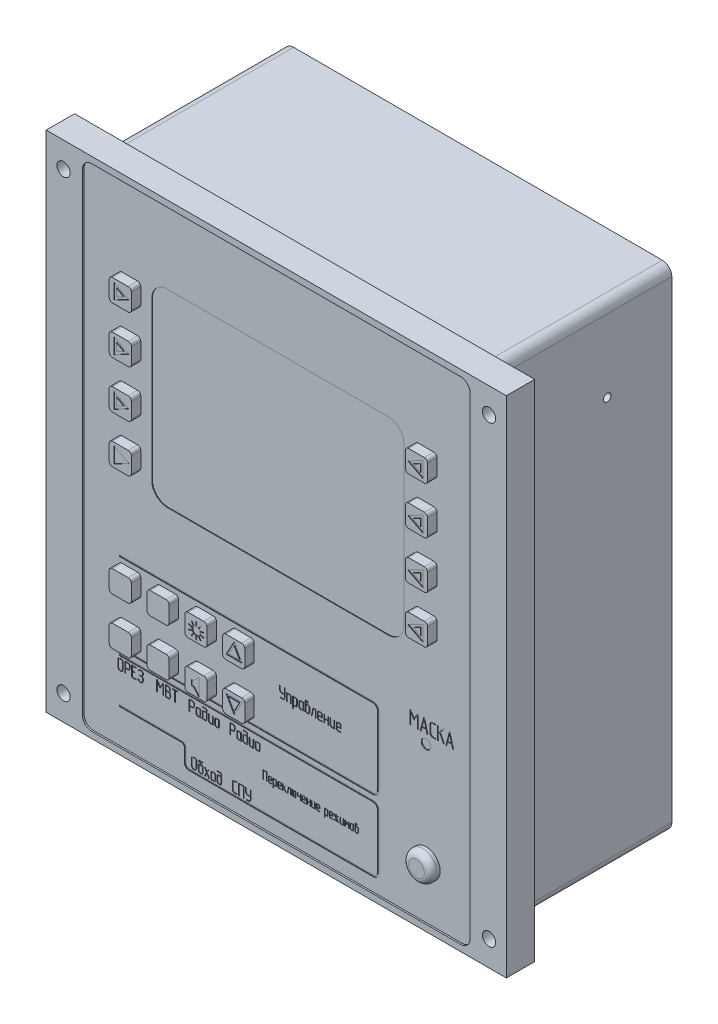
SolidWorks part; units mm, degrees
ref_plane "Спереди" through (0, 0, 0) normal (0, 0, 1) x (1, 0, 0)
ref_plane "Сверху" through (0, 0, 0) normal (0, 1, 0) x (1, 0, 0)
ref_plane "Справа" through (0, 0, 0) normal (1, 0, 0) x (0, 0, -1)
sketch "Эскиз1" plane through (0, 0, 0) normal (0, 0, 1) x (1, 0, 0)
  line L1 (-73, 80) -> (73, 80)
  line L2 (-73, 80) -> (-73, -80)
  line L3 (-73, -80) -> (73, -80)
  line L4 (73, 80) -> (73, -80)
  line L5 (0, -80) -> (0, 80) construction
  line L6 (-73, 0) -> (73, 0) construction
  point P0 (0, 0)
  dimension "D1" = 146
  dimension "D2" = 160
extrude "Бобышка-Вытянуть1" add sketch "Эскиз1" along normal mid plane 9
sketch "Эскиз3" plane through (0, 0, -4.5) normal (0, 0, -1) x (-1, 0, 0)
  line L1 (-61.5, 78) -> (61.5, 78)
  line L2 (-61.5, 78) -> (-61.5, -78)
  line L3 (-61.5, -78) -> (61.5, -78)
  line L4 (61.5, 78) -> (61.5, -78)
  line L5 (0, -78) -> (0, 78) construction
  line L6 (-61.5, 0) -> (61.5, 0) construction
  point P0 (0, 0)
  dimension "D1" = 123
  dimension "D2" = 156
extrude "Бобышка-Вытянуть2" add sketch "Эскиз3" along normal blind 55
fillet "Скругление1" radius 3 4 edges at (-61.5, -78, -32) (61.5, -78, -32) (61.5, 78, -32) (-61.5, 78, -32)
sketch "Эскиз4" plane through (0, 0, -59.5) normal (0, 0, -1) x (-1, 0, 0)
  line L0 (-73, -80) -> (-73, 80) construction
  line L1 (73, -80) -> (-73, -80) construction
  line L2 (-49, -51.3122) -> (-49, -72.7557) construction
  line L3 (-57.2172, -62) -> (-38.8096, -62) construction
  line L5 (-54.9, -56.1) -> (-43.1, -56.1) construction
  line L6 (-54.9, -56.1) -> (-54.9, -67.9) construction
  line L7 (-54.9, -67.9) -> (-43.1, -67.9) construction
  line L8 (-43.1, -56.1) -> (-43.1, -67.9) construction
  line L9 (-49, -67.9) -> (-49, -56.1) construction
  line L10 (-54.9, -62) -> (-43.1, -62) construction
  circle A0 centre (-49, -62) radius 5
  circle A1 centre (-54.9, -56.1) radius 1.1
  circle A2 centre (-43.1, -56.1) radius 1.1
  circle A3 centre (-43.1, -67.9) radius 1.1
  circle A4 centre (-54.9, -67.9) radius 1.1
  dimension "D1" = 24
  dimension "D2" = 18
  dimension "D3" = 10
  dimension "D5" = 2.2
  dimension "D6" = 11.8
  dimension "D4" = 11.8
extrude "Вырез-Вытянуть1" cut sketch "Эскиз4" against normal blind 20
sketch "Эскиз5" plane through (0, 0, -59.5) normal (0, 0, -1) x (-1, 0, 0)
  line L0 (-73, -80) -> (-73, 80) construction
  line L1 (73, -80) -> (-73, -80) construction
  line L3 (-53.75, 71.5) -> (-32.25, 71.5) construction
  line L4 (-53.75, 71.5) -> (-53.75, 50) construction
  line L5 (-53.75, 50) -> (-32.25, 50) construction
  line L6 (-32.25, 71.5) -> (-32.25, 50) construction
  line L7 (-43, 50) -> (-43, 71.5) construction
  line L8 (-53.75, 60.75) -> (-32.25, 60.75) construction
  circle A0 centre (-43, 60.75) radius 11
  circle A1 centre (-53.75, 71.5) radius 1.35
  circle A2 centre (-32.25, 71.5) radius 1.35
  circle A3 centre (-32.25, 50) radius 1.35
  circle A4 centre (-53.75, 50) radius 1.35
  dimension "D1" = 22
  dimension "D2" = 30
  dimension "D3" = 140.75
  dimension "D5" = 2.7
  dimension "D6" = 21.5
  dimension "D4" = 21.5
extrude "Вырез-Вытянуть2" cut sketch "Эскиз5" against normal blind 20
sketch "Эскиз6" plane through (0, 0, 4.5) normal (0, 0, 1) x (1, 0, 0)
  line L0 (67.5, 72) -> (67.5, -72) construction
  line L1 (-67.5, 72) -> (67.5, 72) construction
  line L3 (-67.5, -72) -> (67.5, -72) construction
  line L5 (0, -72) -> (0, 72) construction
  line L6 (-67.5, 0) -> (67.5, 0) construction
  line L7 (-67.5, 72) -> (-67.5, -72) construction
  circle A0 centre (-67.5, 72) radius 2.1
  circle A1 centre (67.5, 72) radius 2.1
  circle A2 centre (67.5, -72) radius 2.1
  circle A3 centre (-67.5, -72) radius 2.1
  point P1 (0, 0)
  dimension "D3" = 4.2
  dimension "D1" = 135
  dimension "D2" = 144
extrude "Вырез-Вытянуть3" cut sketch "Эскиз6" against normal blind 20
sketch "Эскиз7" plane through (61.5, 0, 0) normal (1, 0, 0) x (0, 0, -1)
  circle A0 centre (14, 52) radius 1.2
  circle A1 centre (39, 52) radius 1.2
extrude "Вырез-Вытянуть4" cut sketch "Эскиз7" against normal blind 10
sketch "Эскиз8" plane through (0, 0, 4.5) normal (0, 0, 1) x (1, 0, 0)
  line L27 (-61.5, 75) -> (-61.5, -75)
  line L28 (-58.5, -78) -> (58.5, -78)
  line L29 (61.5, -75) -> (61.5, 75)
  line L30 (58.5, 78) -> (-58.5, 78)
  line L31 (-61.5, 75) -> (-61.5, -75)
  line L32 (-58.5, -78) -> (58.5, -78)
  line L33 (61.5, -75) -> (61.5, 75)
  line L34 (58.5, 78) -> (-58.5, 78)
  arc A21 (-58.5, 78) -> (-61.5, 75) centre (-58.5, 75) ccw
  arc A22 (-61.5, -75) -> (-58.5, -78) centre (-58.5, -75) ccw
  arc A23 (58.5, -78) -> (61.5, -75) centre (58.5, -75) ccw
  arc A24 (61.5, 75) -> (58.5, 78) centre (58.5, 75) ccw
  arc A25 (-58.5, 78) -> (-61.5, 75) centre (-58.5, 75) ccw
  arc A26 (-61.5, -75) -> (-58.5, -78) centre (-58.5, -75) ccw
  arc A27 (58.5, -78) -> (61.5, -75) centre (58.5, -75) ccw
  arc A28 (61.5, 75) -> (58.5, 78) centre (58.5, 75) ccw
  dimension "D1" = 0
extrude "Вырез-Вытянуть5" cut sketch "Эскиз8" against normal blind 0.5
sketch "Эскиз9" plane through (0, 0, 4) normal (0, 0, 1) x (1, 0, 0)
  line L1 (-35, 55) -> (35, 55)
  line L2 (-40, 50) -> (-40, 0)
  line L3 (-35, -5) -> (35, -5)
  line L4 (40, 50) -> (40, 0)
  line L5 (0, -5) -> (0, 55) construction
  line L6 (-40, 25) -> (40, 25) construction
  arc A0 (40, 0) -> (35, -5) centre (35, 0) cw
  arc A1 (-35, -5) -> (-40, 0) centre (-35, 0) cw
  arc A2 (40, 50) -> (35, 55) centre (35, 50) ccw
  arc A3 (-35, 55) -> (-40, 50) centre (-35, 50) ccw
  point P0 (0, 25)
  point P7 (40, -5)
  point P12 (40, 55)
  point P16 (-40, 55)
  dimension "D4" = 5
  dimension "D1" = 80
  dimension "D2" = 60
  dimension "D3" = 25
extrude "Вырез-Вытянуть6" cut sketch "Эскиз9" against normal blind 0.2
sketch "Эскиз10" plane through (0, 0, 4) normal (0, 0, 1) x (1, 0, 0)
  line L0 (-1004.6264, 49) -> (48995.3736, 49) construction
  line L1 (-1003.9169, 34) -> (48996.0831, 34) construction
  line L2 (-1000.7748, 19) -> (48999.2252, 19) construction
  line L3 (-999.0517, 4) -> (49000.9483, 4) construction
  line L4 (-35, -5) -> (35, -5) construction
  line L6 (-47, -960.1095) -> (-47, 49039.8905) construction
  line L7 (47, -961.5286) -> (47, 49038.4714) construction
  line L8 (40, 0) -> (40, 50) construction
  line L9 (-40, 50) -> (-40, 0) construction
  line L10 (0, 55) -> (0, -5) construction
  line L11 (-49.5, 52.5) -> (-44.5, 52.5)
  line L12 (-50.5, 51.5) -> (-50.5, 46.5)
  line L13 (-49.5, 45.5) -> (-44.5, 45.5)
  line L14 (-43.5, 51.5) -> (-43.5, 46.5)
  line L15 (-47, 45.5) -> (-47, 52.5) construction
  line L16 (-50.5, 49) -> (-43.5, 49) construction
  line L17 (35, 55) -> (-35, 55) construction
  line L18 (-50.5, 36.5) -> (-50.5, 31.5)
  line L19 (-49.5, 37.5) -> (-44.5, 37.5)
  line L20 (-43.5, 36.5) -> (-43.5, 31.5)
  line L21 (-49.5, 30.5) -> (-44.5, 30.5)
  line L22 (-50.5, 21.5) -> (-50.5, 16.5)
  line L23 (-49.5, 22.5) -> (-44.5, 22.5)
  line L24 (-43.5, 21.5) -> (-43.5, 16.5)
  line L25 (-49.5, 15.5) -> (-44.5, 15.5)
  line L26 (-50.5, 6.5) -> (-50.5, 1.5)
  line L27 (-49.5, 7.5) -> (-44.5, 7.5)
  line L28 (-43.5, 6.5) -> (-43.5, 1.5)
  line L29 (-49.5, 0.5) -> (-44.5, 0.5)
  line L30 (50.5, 49) -> (43.5, 49) construction
  line L31 (47, 45.5) -> (47, 52.5) construction
  line L32 (49.5, 0.5) -> (44.5, 0.5)
  line L33 (43.5, 6.5) -> (43.5, 1.5)
  line L34 (49.5, 7.5) -> (44.5, 7.5)
  line L35 (50.5, 6.5) -> (50.5, 1.5)
  line L36 (49.5, 15.5) -> (44.5, 15.5)
  line L37 (43.5, 21.5) -> (43.5, 16.5)
  line L38 (49.5, 22.5) -> (44.5, 22.5)
  line L39 (50.5, 21.5) -> (50.5, 16.5)
  line L40 (49.5, 30.5) -> (44.5, 30.5)
  line L41 (43.5, 36.5) -> (43.5, 31.5)
  line L42 (49.5, 37.5) -> (44.5, 37.5)
  line L43 (50.5, 36.5) -> (50.5, 31.5)
  line L44 (43.5, 51.5) -> (43.5, 46.5)
  line L45 (49.5, 45.5) -> (44.5, 45.5)
  line L46 (50.5, 51.5) -> (50.5, 46.5)
  line L47 (49.5, 52.5) -> (44.5, 52.5)
  line L48 (-120.7943, -31) -> (106.8972, -31) construction
  line L49 (-120.7943, -46) -> (106.8972, -46) construction
  line L50 (-35, -10.082) -> (-35, -66.0065) construction
  line L51 (-23, -10.082) -> (-23, -66.0065) construction
  line L52 (-37.5, -27.5) -> (-32.5, -27.5)
  line L53 (-49.5, -27.5) -> (-44.5, -27.5)
  line L54 (-50.5, -28.5) -> (-50.5, -33.5)
  line L55 (-49.5, -34.5) -> (-44.5, -34.5)
  line L56 (-43.5, -28.5) -> (-43.5, -33.5)
  line L57 (-47, -34.5) -> (-47, -27.5) construction
  line L58 (-50.5, -31) -> (-43.5, -31) construction
  line L59 (-38.5, -28.5) -> (-38.5, -33.5)
  line L60 (-37.5, -34.5) -> (-32.5, -34.5)
  line L61 (-31.5, -28.5) -> (-31.5, -33.5)
  line L62 (-35, -34.5) -> (-35, -27.5) construction
  line L63 (-38.5, -31) -> (-31.5, -31) construction
  line L64 (-25.5, -27.5) -> (-20.5, -27.5)
  line L65 (-26.5, -28.5) -> (-26.5, -33.5)
  line L66 (-25.5, -34.5) -> (-20.5, -34.5)
  line L67 (-19.5, -28.5) -> (-19.5, -33.5)
  line L68 (-23, -34.5) -> (-23, -27.5) construction
  line L69 (-26.5, -31) -> (-19.5, -31) construction
  line L70 (-13.5, -27.5) -> (-8.5, -27.5)
  line L71 (-14.5, -28.5) -> (-14.5, -33.5)
  line L72 (-13.5, -34.5) -> (-8.5, -34.5)
  line L73 (-7.5, -28.5) -> (-7.5, -33.5)
  line L74 (-11, -34.5) -> (-11, -27.5) construction
  line L75 (-14.5, -31) -> (-7.5, -31) construction
  line L76 (-37.5, -42.5) -> (-32.5, -42.5)
  line L77 (-38.5, -43.5) -> (-38.5, -48.5)
  line L78 (-37.5, -49.5) -> (-32.5, -49.5)
  line L79 (-31.5, -43.5) -> (-31.5, -48.5)
  line L80 (-35, -49.5) -> (-35, -42.5) construction
  line L81 (-38.5, -46) -> (-31.5, -46) construction
  line L82 (-25.5, -42.5) -> (-20.5, -42.5)
  line L83 (-26.5, -43.5) -> (-26.5, -48.5)
  line L84 (-25.5, -49.5) -> (-20.5, -49.5)
  line L85 (-19.5, -43.5) -> (-19.5, -48.5)
  line L86 (-23, -49.5) -> (-23, -42.5) construction
  line L87 (-26.5, -46) -> (-19.5, -46) construction
  line L88 (-13.5, -42.5) -> (-8.5, -42.5)
  line L89 (-14.5, -43.5) -> (-14.5, -48.5)
  line L90 (-13.5, -49.5) -> (-8.5, -49.5)
  line L91 (-7.5, -43.5) -> (-7.5, -48.5)
  line L92 (-11, -49.5) -> (-11, -42.5) construction
  line L93 (-14.5, -46) -> (-7.5, -46) construction
  line L94 (-49.5, -42.5) -> (-44.5, -42.5)
  line L95 (-50.5, -43.5) -> (-50.5, -48.5)
  line L96 (-49.5, -49.5) -> (-44.5, -49.5)
  line L97 (-43.5, -43.5) -> (-43.5, -48.5)
  line L98 (-47, -49.5) -> (-47, -42.5) construction
  line L99 (-50.5, -46) -> (-43.5, -46) construction
  arc A0 (-43.5, 46.5) -> (-44.5, 45.5) centre (-44.5, 46.5) cw
  arc A1 (-49.5, 45.5) -> (-50.5, 46.5) centre (-49.5, 46.5) cw
  arc A2 (-43.5, 51.5) -> (-44.5, 52.5) centre (-44.5, 51.5) ccw
  arc A3 (-50.5, 51.5) -> (-49.5, 52.5) centre (-49.5, 51.5) cw
  arc A4 (-50.5, 36.5) -> (-49.5, 37.5) centre (-49.5, 36.5) cw
  arc A5 (-43.5, 36.5) -> (-44.5, 37.5) centre (-44.5, 36.5) ccw
  arc A6 (-43.5, 31.5) -> (-44.5, 30.5) centre (-44.5, 31.5) cw
  arc A7 (-49.5, 30.5) -> (-50.5, 31.5) centre (-49.5, 31.5) cw
  arc A8 (-50.5, 21.5) -> (-49.5, 22.5) centre (-49.5, 21.5) cw
  arc A9 (-43.5, 21.5) -> (-44.5, 22.5) centre (-44.5, 21.5) ccw
  arc A10 (-43.5, 16.5) -> (-44.5, 15.5) centre (-44.5, 16.5) cw
  arc A11 (-49.5, 15.5) -> (-50.5, 16.5) centre (-49.5, 16.5) cw
  arc A12 (-50.5, 6.5) -> (-49.5, 7.5) centre (-49.5, 6.5) cw
  arc A13 (-43.5, 6.5) -> (-44.5, 7.5) centre (-44.5, 6.5) ccw
  arc A14 (-43.5, 1.5) -> (-44.5, 0.5) centre (-44.5, 1.5) cw
  arc A15 (-49.5, 0.5) -> (-50.5, 1.5) centre (-49.5, 1.5) cw
  arc A16 (49.5, 0.5) -> (50.5, 1.5) centre (49.5, 1.5) ccw
  arc A17 (43.5, 1.5) -> (44.5, 0.5) centre (44.5, 1.5) ccw
  arc A18 (43.5, 6.5) -> (44.5, 7.5) centre (44.5, 6.5) cw
  arc A19 (50.5, 6.5) -> (49.5, 7.5) centre (49.5, 6.5) ccw
  arc A20 (49.5, 15.5) -> (50.5, 16.5) centre (49.5, 16.5) ccw
  arc A21 (43.5, 16.5) -> (44.5, 15.5) centre (44.5, 16.5) ccw
  arc A22 (43.5, 21.5) -> (44.5, 22.5) centre (44.5, 21.5) cw
  arc A23 (50.5, 21.5) -> (49.5, 22.5) centre (49.5, 21.5) ccw
  arc A24 (49.5, 30.5) -> (50.5, 31.5) centre (49.5, 31.5) ccw
  arc A25 (43.5, 31.5) -> (44.5, 30.5) centre (44.5, 31.5) ccw
  arc A26 (43.5, 36.5) -> (44.5, 37.5) centre (44.5, 36.5) cw
  arc A27 (50.5, 36.5) -> (49.5, 37.5) centre (49.5, 36.5) ccw
  arc A28 (50.5, 51.5) -> (49.5, 52.5) centre (49.5, 51.5) ccw
  arc A29 (43.5, 51.5) -> (44.5, 52.5) centre (44.5, 51.5) cw
  arc A30 (49.5, 45.5) -> (50.5, 46.5) centre (49.5, 46.5) ccw
  arc A31 (43.5, 46.5) -> (44.5, 45.5) centre (44.5, 46.5) ccw
  arc A32 (-50.5, -33.5) -> (-49.5, -34.5) centre (-49.5, -33.5) ccw
  arc A33 (-43.5, -33.5) -> (-44.5, -34.5) centre (-44.5, -33.5) cw
  arc A34 (-43.5, -28.5) -> (-44.5, -27.5) centre (-44.5, -28.5) ccw
  arc A35 (-49.5, -27.5) -> (-50.5, -28.5) centre (-49.5, -28.5) ccw
  arc A36 (-38.5, -33.5) -> (-37.5, -34.5) centre (-37.5, -33.5) ccw
  arc A37 (-31.5, -33.5) -> (-32.5, -34.5) centre (-32.5, -33.5) cw
  arc A38 (-31.5, -28.5) -> (-32.5, -27.5) centre (-32.5, -28.5) ccw
  arc A39 (-37.5, -27.5) -> (-38.5, -28.5) centre (-37.5, -28.5) ccw
  arc A40 (-26.5, -33.5) -> (-25.5, -34.5) centre (-25.5, -33.5) ccw
  arc A41 (-19.5, -33.5) -> (-20.5, -34.5) centre (-20.5, -33.5) cw
  arc A42 (-19.5, -28.5) -> (-20.5, -27.5) centre (-20.5, -28.5) ccw
  arc A43 (-25.5, -27.5) -> (-26.5, -28.5) centre (-25.5, -28.5) ccw
  arc A44 (-14.5, -33.5) -> (-13.5, -34.5) centre (-13.5, -33.5) ccw
  arc A45 (-7.5, -33.5) -> (-8.5, -34.5) centre (-8.5, -33.5) cw
  arc A46 (-7.5, -28.5) -> (-8.5, -27.5) centre (-8.5, -28.5) ccw
  arc A47 (-13.5, -27.5) -> (-14.5, -28.5) centre (-13.5, -28.5) ccw
  arc A48 (-38.5, -48.5) -> (-37.5, -49.5) centre (-37.5, -48.5) ccw
  arc A49 (-31.5, -48.5) -> (-32.5, -49.5) centre (-32.5, -48.5) cw
  arc A50 (-31.5, -43.5) -> (-32.5, -42.5) centre (-32.5, -43.5) ccw
  arc A51 (-37.5, -42.5) -> (-38.5, -43.5) centre (-37.5, -43.5) ccw
  arc A52 (-26.5, -48.5) -> (-25.5, -49.5) centre (-25.5, -48.5) ccw
  arc A53 (-19.5, -48.5) -> (-20.5, -49.5) centre (-20.5, -48.5) cw
  arc A54 (-19.5, -43.5) -> (-20.5, -42.5) centre (-20.5, -43.5) ccw
  arc A55 (-25.5, -42.5) -> (-26.5, -43.5) centre (-25.5, -43.5) ccw
  arc A56 (-14.5, -48.5) -> (-13.5, -49.5) centre (-13.5, -48.5) ccw
  arc A57 (-7.5, -48.5) -> (-8.5, -49.5) centre (-8.5, -48.5) cw
  arc A58 (-7.5, -43.5) -> (-8.5, -42.5) centre (-8.5, -43.5) ccw
  arc A59 (-13.5, -42.5) -> (-14.5, -43.5) centre (-13.5, -43.5) ccw
  arc A60 (-50.5, -48.5) -> (-49.5, -49.5) centre (-49.5, -48.5) ccw
  arc A61 (-43.5, -48.5) -> (-44.5, -49.5) centre (-44.5, -48.5) cw
  arc A62 (-43.5, -43.5) -> (-44.5, -42.5) centre (-44.5, -43.5) ccw
  arc A63 (-49.5, -42.5) -> (-50.5, -43.5) centre (-49.5, -43.5) ccw
  point P18 (-47, 49)
  point P24 (-43.5, 45.5)
  point P29 (-43.5, 52.5)
  point P33 (-50.5, 52.5)
  point P130 (50.5, 52.5)
  point P131 (43.5, 52.5)
  point P132 (43.5, 45.5)
  point P133 (47, 49)
  point P142 (-47, -31)
  point P150 (-43.5, -34.5)
  point P153 (-43.5, -27.5)
  point P157 (-50.5, -27.5)
  point P161 (-35, -31)
  point P178 (-23, -31)
  point P195 (-11, -31)
  point P216 (-35, -46)
  point P233 (-23, -46)
  point P250 (-11, -46)
  point P267 (-47, -46)
  dimension "D9" = 1
  dimension "D17" = 1
  dimension "D1" = 9
  dimension "D2" = 15
  dimension "D3" = 15
  dimension "D4" = 15
  dimension "D5" = 7
  dimension "D6" = 7
  dimension "D7" = 7
  dimension "D8" = 7
  dimension "D11" = 35
  dimension "D12" = 15
  dimension "D13" = 12
  dimension "D14" = 12
  dimension "D15" = 7
  dimension "D16" = 7
  dimension "D10" = 4
  dimension "D18" = 4
  dimension "D19" = 2
extrude "Бобышка-Вытянуть3" add sketch "Эскиз10" along normal blind 3
sketch "Эскиз11" plane through (0, 0, 4) normal (0, 0, 1) x (1, 0, 0)
  line L0 (47, 7.5) -> (47, -102.5) construction
  line L1 (49.5, 7.5) -> (44.5, 7.5) construction
  circle A0 centre (47, -61.6571) radius 4.5
  point P2 (0, 0)
  dimension "D1" = 9
extrude "Бобышка-Вытянуть4" add sketch "Эскиз11" along normal blind 3
fillet "Скругление2" radius 2 1 edges at (51.5, -61.6571, 7)
sketch "Эскиз12" plane through (0, 0, 4) normal (0, 0, 1) x (1, 0, 0)
  line L0 (47, 7.5) -> (47, -50.0468) construction
  line L1 (49.5, 7.5) -> (44.5, 7.5) construction
  line L3 (-8.5, -27.5) -> (-13.5, -27.5) construction
  circle A0 centre (47, -29) radius 1.5
  point P6 (0, 0)
  dimension "D1" = 3
extrude "Вырез-Вытянуть7" cut sketch "Эскиз12" against normal blind 0.3
sketch "Эскиз13" plane through (0, 0, 7) normal (0, 0, 1) x (1, 0, 0)
  line L0 (-49.0227, 51.5) -> (-49.0227, 46.4952)
  line L1 (-49.0227, 46.4952) -> (-44.2167, 48.9976)
  line L2 (-44.2167, 48.9976) -> (-49.0227, 51.5)
  line L3 (-45.9489, 48.9976) -> (-48.2227, 50.1815)
  line L4 (-48.2227, 50.1815) -> (-48.2227, 47.8137)
  line L5 (-48.2227, 47.8137) -> (-45.9489, 48.9976)
  line L12 (-49.0227, 51.4841) -> (-49.0227, 46.4792)
  line L13 (-49.0227, 46.4792) -> (-44.2167, 48.9817)
  line L14 (-44.2167, 48.9817) -> (-49.0227, 51.4841)
  line L15 (-45.9489, 48.9817) -> (-48.2227, 50.1656)
  line L16 (-48.2227, 50.1656) -> (-48.2227, 47.7977)
  line L17 (-48.2227, 47.7977) -> (-45.9489, 48.9817)
  line L18 (-49.0227, 51.4682) -> (-49.0227, 46.4633)
  line L19 (-49.0227, 46.4633) -> (-44.2167, 48.9657)
  line L20 (-44.2167, 48.9657) -> (-49.0227, 51.4682)
  line L21 (-45.9489, 48.9657) -> (-48.2227, 50.1497)
  line L22 (-48.2227, 50.1497) -> (-48.2227, 47.7818)
  line L23 (-48.2227, 47.7818) -> (-45.9489, 48.9657)
  line L24 (-49.0227, 51.4523) -> (-49.0227, 46.4474)
  line L25 (-49.0227, 46.4474) -> (-44.2167, 48.9498)
  line L26 (-44.2167, 48.9498) -> (-49.0227, 51.4523)
  line L27 (-45.9489, 48.9498) -> (-48.2227, 50.1337)
  line L28 (-48.2227, 50.1337) -> (-48.2227, 47.7659)
  line L29 (-48.2227, 47.7659) -> (-45.9489, 48.9498)
  line L30 (0, 55) -> (0, -5) construction
  line L31 (35, 55) -> (-35, 55) construction
  line L32 (-35, -5) -> (35, -5) construction
  line L33 (48.2227, 47.7659) -> (45.9489, 48.9498)
  line L34 (48.2227, 50.1337) -> (48.2227, 47.7659)
  line L35 (45.9489, 48.9498) -> (48.2227, 50.1337)
  line L36 (44.2167, 48.9498) -> (49.0227, 51.4523)
  line L37 (49.0227, 46.4474) -> (44.2167, 48.9498)
  line L38 (49.0227, 51.4523) -> (49.0227, 46.4474)
  line L39 (48.2227, 47.7818) -> (45.9489, 48.9657)
  line L40 (48.2227, 50.1497) -> (48.2227, 47.7818)
  line L41 (45.9489, 48.9657) -> (48.2227, 50.1497)
  line L42 (44.2167, 48.9657) -> (49.0227, 51.4682)
  line L43 (49.0227, 46.4633) -> (44.2167, 48.9657)
  line L44 (49.0227, 51.4682) -> (49.0227, 46.4633)
  line L45 (48.2227, 47.7977) -> (45.9489, 48.9817)
  line L46 (48.2227, 50.1656) -> (48.2227, 47.7977)
  line L47 (45.9489, 48.9817) -> (48.2227, 50.1656)
  line L48 (44.2167, 48.9817) -> (49.0227, 51.4841)
  line L49 (49.0227, 46.4792) -> (44.2167, 48.9817)
  line L50 (49.0227, 51.4841) -> (49.0227, 46.4792)
  line L51 (48.2227, 47.8137) -> (45.9489, 48.9976)
  line L52 (48.2227, 50.1815) -> (48.2227, 47.8137)
  line L53 (45.9489, 48.9976) -> (48.2227, 50.1815)
  line L54 (44.2167, 48.9976) -> (49.0227, 51.5)
  line L55 (49.0227, 46.4952) -> (44.2167, 48.9976)
  line L56 (49.0227, 51.5) -> (49.0227, 46.4952)
  line L57 (-49.9873, -32.8529) -> (-43.8552, -32.8529) construction
  line L58 (-49.0227, 36.5) -> (-49.0227, 31.4952)
  line L60 (-49.0227, 31.4952) -> (-44.2167, 33.9976)
  line L61 (-44.2167, 33.9976) -> (-49.0227, 36.5)
  line L64 (-45.9489, 33.9976) -> (-48.2227, 35.1815)
  line L65 (-48.2227, 35.1815) -> (-48.2227, 32.8137)
  line L66 (-48.2227, 32.8137) -> (-45.9489, 33.9976)
  line L67 (-49.0227, 36.4841) -> (-49.0227, 31.4792)
  line L68 (-49.0227, 31.4792) -> (-44.2167, 33.9817)
  line L69 (-44.2167, 33.9817) -> (-49.0227, 36.4841)
  line L70 (-45.9489, 33.9817) -> (-48.2227, 35.1656)
  line L71 (-48.2227, 35.1656) -> (-48.2227, 32.7977)
  line L72 (-48.2227, 32.7977) -> (-45.9489, 33.9817)
  line L73 (-49.0227, 36.4682) -> (-49.0227, 31.4633)
  line L74 (-49.0227, 31.4633) -> (-44.2167, 33.9657)
  line L75 (-44.2167, 33.9657) -> (-49.0227, 36.4682)
  line L76 (-45.9489, 33.9657) -> (-48.2227, 35.1497)
  line L77 (-48.2227, 35.1497) -> (-48.2227, 32.7818)
  line L78 (-48.2227, 32.7818) -> (-45.9489, 33.9657)
  line L79 (-49.0227, 36.4523) -> (-49.0227, 31.4474)
  line L80 (-49.0227, 31.4474) -> (-44.2167, 33.9498)
  line L81 (-44.2167, 33.9498) -> (-49.0227, 36.4523)
  line L82 (-45.9489, 33.9498) -> (-48.2227, 35.1337)
  line L83 (-48.2227, 35.1337) -> (-48.2227, 32.7659)
  line L84 (-48.2227, 32.7659) -> (-45.9489, 33.9498)
  line L85 (-49.0227, 21.5) -> (-49.0227, 16.4952)
  line L86 (-49.0227, 16.4952) -> (-44.2167, 18.9976)
  line L87 (-44.2167, 18.9976) -> (-49.0227, 21.5)
  line L88 (-45.9489, 18.9976) -> (-48.2227, 20.1815)
  line L89 (-48.2227, 20.1815) -> (-48.2227, 17.8137)
  line L90 (-48.2227, 17.8137) -> (-45.9489, 18.9976)
  line L91 (-49.0227, 21.4841) -> (-49.0227, 16.4792)
  line L92 (-49.0227, 16.4792) -> (-44.2167, 18.9817)
  line L93 (-44.2167, 18.9817) -> (-49.0227, 21.4841)
  line L94 (-45.9489, 18.9817) -> (-48.2227, 20.1656)
  line L95 (-48.2227, 20.1656) -> (-48.2227, 17.7977)
  line L96 (-48.2227, 17.7977) -> (-45.9489, 18.9817)
  line L97 (-49.0227, 21.4682) -> (-49.0227, 16.4633)
  line L98 (-49.0227, 16.4633) -> (-44.2167, 18.9657)
  line L99 (-44.2167, 18.9657) -> (-49.0227, 21.4682)
  line L100 (-45.9489, 18.9657) -> (-48.2227, 20.1497)
  line L101 (-48.2227, 20.1497) -> (-48.2227, 17.7818)
  line L102 (-48.2227, 17.7818) -> (-45.9489, 18.9657)
  line L103 (-49.0227, 21.4523) -> (-49.0227, 16.4474)
  line L104 (-49.0227, 16.4474) -> (-44.2167, 18.9498)
  line L105 (-44.2167, 18.9498) -> (-49.0227, 21.4523)
  line L106 (-45.9489, 18.9498) -> (-48.2227, 20.1337)
  line L107 (-48.2227, 20.1337) -> (-48.2227, 17.7659)
  line L108 (-48.2227, 17.7659) -> (-45.9489, 18.9498)
  line L109 (-49.0227, 6.5) -> (-49.0227, 1.4952)
  line L110 (-49.0227, 1.4952) -> (-44.2167, 3.9976)
  line L111 (-44.2167, 3.9976) -> (-49.0227, 6.5)
  line L112 (-45.9489, 3.9976) -> (-48.2227, 5.1815)
  line L113 (-48.2227, 5.1815) -> (-48.2227, 2.8137)
  line L114 (-48.2227, 2.8137) -> (-45.9489, 3.9976)
  line L115 (-49.0227, 6.4841) -> (-49.0227, 1.4792)
  line L116 (-49.0227, 1.4792) -> (-44.2167, 3.9817)
  line L117 (-44.2167, 3.9817) -> (-49.0227, 6.4841)
  line L118 (-45.9489, 3.9817) -> (-48.2227, 5.1656)
  line L119 (-48.2227, 5.1656) -> (-48.2227, 2.7977)
  line L120 (-48.2227, 2.7977) -> (-45.9489, 3.9817)
  line L121 (-49.0227, 6.4682) -> (-49.0227, 1.4633)
  line L122 (-49.0227, 1.4633) -> (-44.2167, 3.9657)
  line L123 (-44.2167, 3.9657) -> (-49.0227, 6.4682)
  line L124 (-45.9489, 3.9657) -> (-48.2227, 5.1497)
  line L125 (-48.2227, 5.1497) -> (-48.2227, 2.7818)
  line L126 (-48.2227, 2.7818) -> (-45.9489, 3.9657)
  line L127 (-49.0227, 6.4523) -> (-49.0227, 1.4474)
  line L128 (-49.0227, 1.4474) -> (-44.2167, 3.9498)
  line L129 (-44.2167, 3.9498) -> (-49.0227, 6.4523)
  line L130 (-45.9489, 3.9498) -> (-48.2227, 5.1337)
  line L131 (-48.2227, 5.1337) -> (-48.2227, 2.7659)
  line L132 (-48.2227, 2.7659) -> (-45.9489, 3.9498)
  line L133 (48.2227, 32.7659) -> (45.9489, 33.9498)
  line L134 (48.2227, 35.1337) -> (48.2227, 32.7659)
  line L135 (45.9489, 33.9498) -> (48.2227, 35.1337)
  line L136 (44.2167, 33.9498) -> (49.0227, 36.4523)
  line L137 (49.0227, 31.4474) -> (44.2167, 33.9498)
  line L138 (49.0227, 36.4523) -> (49.0227, 31.4474)
  line L139 (48.2227, 32.7818) -> (45.9489, 33.9657)
  line L140 (48.2227, 35.1497) -> (48.2227, 32.7818)
  line L141 (45.9489, 33.9657) -> (48.2227, 35.1497)
  line L142 (44.2167, 33.9657) -> (49.0227, 36.4682)
  line L143 (49.0227, 31.4633) -> (44.2167, 33.9657)
  line L144 (49.0227, 36.4682) -> (49.0227, 31.4633)
  line L145 (48.2227, 32.7977) -> (45.9489, 33.9817)
  line L146 (48.2227, 35.1656) -> (48.2227, 32.7977)
  line L147 (45.9489, 33.9817) -> (48.2227, 35.1656)
  line L148 (44.2167, 33.9817) -> (49.0227, 36.4841)
  line L149 (49.0227, 31.4792) -> (44.2167, 33.9817)
  line L150 (49.0227, 36.4841) -> (49.0227, 31.4792)
  line L151 (48.2227, 32.8137) -> (45.9489, 33.9976)
  line L152 (48.2227, 35.1815) -> (48.2227, 32.8137)
  line L153 (45.9489, 33.9976) -> (48.2227, 35.1815)
  line L154 (44.2167, 33.9976) -> (49.0227, 36.5)
  line L155 (49.0227, 31.4952) -> (44.2167, 33.9976)
  line L156 (49.0227, 36.5) -> (49.0227, 31.4952)
  line L157 (48.2227, 17.7659) -> (45.9489, 18.9498)
  line L158 (48.2227, 20.1337) -> (48.2227, 17.7659)
  line L159 (45.9489, 18.9498) -> (48.2227, 20.1337)
  line L160 (44.2167, 18.9498) -> (49.0227, 21.4523)
  line L161 (49.0227, 16.4474) -> (44.2167, 18.9498)
  line L162 (49.0227, 21.4523) -> (49.0227, 16.4474)
  line L163 (48.2227, 17.7818) -> (45.9489, 18.9657)
  line L164 (48.2227, 20.1497) -> (48.2227, 17.7818)
  line L165 (45.9489, 18.9657) -> (48.2227, 20.1497)
  line L166 (44.2167, 18.9657) -> (49.0227, 21.4682)
  line L167 (49.0227, 16.4633) -> (44.2167, 18.9657)
  line L168 (49.0227, 21.4682) -> (49.0227, 16.4633)
  line L169 (48.2227, 17.7977) -> (45.9489, 18.9817)
  line L170 (48.2227, 20.1656) -> (48.2227, 17.7977)
  line L171 (45.9489, 18.9817) -> (48.2227, 20.1656)
  line L172 (44.2167, 18.9817) -> (49.0227, 21.4841)
  line L173 (49.0227, 16.4792) -> (44.2167, 18.9817)
  line L174 (49.0227, 21.4841) -> (49.0227, 16.4792)
  line L175 (48.2227, 17.8137) -> (45.9489, 18.9976)
  line L176 (48.2227, 20.1815) -> (48.2227, 17.8137)
  line L177 (45.9489, 18.9976) -> (48.2227, 20.1815)
  line L178 (44.2167, 18.9976) -> (49.0227, 21.5)
  line L179 (49.0227, 16.4952) -> (44.2167, 18.9976)
  line L180 (49.0227, 21.5) -> (49.0227, 16.4952)
  line L181 (48.2227, 2.7659) -> (45.9489, 3.9498)
  line L182 (48.2227, 5.1337) -> (48.2227, 2.7659)
  line L183 (45.9489, 3.9498) -> (48.2227, 5.1337)
  line L184 (44.2167, 3.9498) -> (49.0227, 6.4523)
  line L185 (49.0227, 1.4474) -> (44.2167, 3.9498)
  line L186 (49.0227, 6.4523) -> (49.0227, 1.4474)
  line L187 (48.2227, 2.7818) -> (45.9489, 3.9657)
  line L188 (48.2227, 5.1497) -> (48.2227, 2.7818)
  line L189 (45.9489, 3.9657) -> (48.2227, 5.1497)
  line L190 (44.2167, 3.9657) -> (49.0227, 6.4682)
  line L191 (49.0227, 1.4633) -> (44.2167, 3.9657)
  line L192 (49.0227, 6.4682) -> (49.0227, 1.4633)
  line L193 (48.2227, 2.7977) -> (45.9489, 3.9817)
  line L194 (48.2227, 5.1656) -> (48.2227, 2.7977)
  line L195 (45.9489, 3.9817) -> (48.2227, 5.1656)
  line L196 (44.2167, 3.9817) -> (49.0227, 6.4841)
  line L197 (49.0227, 1.4792) -> (44.2167, 3.9817)
  line L198 (49.0227, 6.4841) -> (49.0227, 1.4792)
  line L199 (48.2227, 2.8137) -> (45.9489, 3.9976)
  line L200 (48.2227, 5.1815) -> (48.2227, 2.8137)
  line L201 (45.9489, 3.9976) -> (48.2227, 5.1815)
  line L202 (44.2167, 3.9976) -> (49.0227, 6.5)
  line L203 (49.0227, 1.4952) -> (44.2167, 3.9976)
  line L204 (49.0227, 6.5) -> (49.0227, 1.4952)
  line L205 (-49.9873, -47.3807) -> (-43.8552, -47.3807) construction
  line L206 (-37.9873, -47.3807) -> (-31.8552, -47.3807) construction
  line L207 (-13.4334, -32.9566) -> (-8.3087, -32.9566)
  line L208 (-8.3087, -32.9566) -> (-10.871, -28.3325)
  line L209 (-10.871, -28.3325) -> (-13.4334, -32.9566)
  line L210 (-9.1574, -32.4566) -> (-10.871, -29.3641)
  line L211 (-10.871, -29.3641) -> (-12.5847, -32.4566)
  line L212 (-12.5847, -32.4566) -> (-9.1574, -32.4566)
  line L213 (-47, -34.5) -> (-47, -42.5) construction
  line L214 (-49.5, -34.5) -> (-44.5, -34.5) construction
  line L215 (-44.5, -42.5) -> (-49.5, -42.5) construction
  line L216 (-50.1701, -38.6196) -> (7.3823, -38.6196) construction
  line L217 (-12.5847, -44.2547) -> (-9.1574, -44.2547)
  line L218 (-10.871, -47.3472) -> (-12.5847, -44.2547)
  line L219 (-9.1574, -44.2547) -> (-10.871, -47.3472)
  line L220 (-10.871, -48.3788) -> (-13.4334, -43.7547)
  line L221 (-8.3087, -43.7547) -> (-10.871, -48.3788)
  line L222 (-13.4334, -43.7547) -> (-8.3087, -43.7547)
  line L223 (-22.9021, -28.9395) -> (-22.9021, -29.8437) construction
  line L224 (-22.7569, -28.9395) -> (-22.7569, -29.8437)
  line L225 (-23.0474, -28.9395) -> (-23.0474, -29.8437)
  line L226 (-21.4939, -29.397) -> (-22.0254, -30.1285) construction
  line L227 (-21.3764, -29.4824) -> (-21.9079, -30.2139)
  line L228 (-21.6114, -29.3116) -> (-22.1429, -30.0432)
  line L229 (-20.6236, -30.5949) -> (-21.4835, -30.8743) construction
  line L230 (-20.5787, -30.733) -> (-21.4387, -31.0124)
  line L231 (-20.6685, -30.4568) -> (-21.5284, -30.7362)
  line L232 (-20.6236, -32.0756) -> (-21.4835, -31.7962) construction
  line L233 (-20.6685, -32.2137) -> (-21.5284, -31.9343)
  line L234 (-20.5787, -31.9375) -> (-21.4387, -31.658)
  line L235 (-21.4939, -33.2735) -> (-22.0254, -32.542) construction
  line L236 (-21.6114, -33.3588) -> (-22.1429, -32.6273)
  line L237 (-21.3764, -33.1881) -> (-21.9079, -32.4566)
  line L238 (-22.9021, -33.731) -> (-22.9021, -32.8268) construction
  line L239 (-23.0474, -33.731) -> (-23.0474, -32.8268)
  line L240 (-22.7569, -33.731) -> (-22.7569, -32.8268)
  line L241 (-24.3103, -33.2735) -> (-23.7789, -32.542) construction
  line L242 (-24.4278, -33.1881) -> (-23.8964, -32.4566)
  line L243 (-24.1928, -33.3588) -> (-23.6614, -32.6273)
  line L244 (-25.1807, -32.0756) -> (-24.3207, -31.7962) construction
  line L245 (-25.2255, -31.9375) -> (-24.3656, -31.658)
  line L246 (-25.1358, -32.2137) -> (-24.2758, -31.9343)
  line L247 (-25.1807, -30.5949) -> (-24.3207, -30.8743) construction
  line L248 (-25.1358, -30.4568) -> (-24.2758, -30.7362)
  line L249 (-25.2255, -30.733) -> (-24.3656, -31.0124)
  line L250 (-24.3103, -29.397) -> (-23.7789, -30.1285) construction
  line L251 (-24.1928, -29.3116) -> (-23.6614, -30.0432)
  line L252 (-24.4278, -29.4824) -> (-23.8964, -30.2139)
  line L253 (-24.3621, -45.3677) -> (-24.3621, -47.0785)
  line L254 (-24.3621, -47.0785) -> (-23.7877, -47.0785)
  line L256 (-23.7877, -45.3677) -> (-24.3621, -45.3677)
  line L257 (-23.7877, -45.3677) -> (-22.0672, -43.6472)
  line L258 (-23.7877, -47.0785) -> (-22.0672, -49.1504)
  line L259 (-22.0672, -49.1504) -> (-22.0672, -43.6472)
  circle A0 centre (-22.9021, -31.3352) radius 1.283
  arc A1 (-22.7569, -28.9395) -> (-23.0474, -28.9395) centre (-22.9021, -28.9395) ccw
  arc A2 (-23.0474, -29.8437) -> (-22.7569, -29.8437) centre (-22.9021, -29.8437) ccw
  arc A3 (-21.3764, -29.4824) -> (-21.6114, -29.3116) centre (-21.4939, -29.397) ccw
  arc A4 (-22.1429, -30.0432) -> (-21.9079, -30.2139) centre (-22.0254, -30.1285) ccw
  arc A5 (-20.5787, -30.733) -> (-20.6685, -30.4568) centre (-20.6236, -30.5949) ccw
  arc A6 (-21.5284, -30.7362) -> (-21.4387, -31.0124) centre (-21.4835, -30.8743) ccw
  arc A7 (-20.6685, -32.2137) -> (-20.5787, -31.9375) centre (-20.6236, -32.0756) ccw
  arc A8 (-21.4387, -31.658) -> (-21.5284, -31.9343) centre (-21.4835, -31.7962) ccw
  arc A9 (-21.6114, -33.3588) -> (-21.3764, -33.1881) centre (-21.4939, -33.2735) ccw
  arc A10 (-21.9079, -32.4566) -> (-22.1429, -32.6273) centre (-22.0254, -32.542) ccw
  arc A11 (-23.0474, -33.731) -> (-22.7569, -33.731) centre (-22.9021, -33.731) ccw
  arc A12 (-22.7569, -32.8268) -> (-23.0474, -32.8268) centre (-22.9021, -32.8268) ccw
  arc A13 (-24.4278, -33.1881) -> (-24.1928, -33.3588) centre (-24.3103, -33.2735) ccw
  arc A14 (-23.6614, -32.6273) -> (-23.8964, -32.4566) centre (-23.7789, -32.542) ccw
  arc A15 (-25.2255, -31.9375) -> (-25.1358, -32.2137) centre (-25.1807, -32.0756) ccw
  arc A16 (-24.2758, -31.9343) -> (-24.3656, -31.658) centre (-24.3207, -31.7962) ccw
  arc A17 (-25.1358, -30.4568) -> (-25.2255, -30.733) centre (-25.1807, -30.5949) ccw
  arc A18 (-24.3656, -31.0124) -> (-24.2758, -30.7362) centre (-24.3207, -30.8743) ccw
  arc A19 (-24.1928, -29.3116) -> (-24.4278, -29.4824) centre (-24.3103, -29.397) ccw
  arc A20 (-23.8964, -30.2139) -> (-23.6614, -30.0432) centre (-23.7789, -30.1285) ccw
  text T0 "РС" font "Arial" height in points 12
  text T2 "ВС" font "Arial" height in points 12
  text T3 "КОНТ" font "Arial Narrow" height in points 8
  point P237 (-22.9021, -29.3916)
  point P246 (-21.7597, -29.7628)
  point P253 (-21.0536, -30.7346)
  point P260 (-21.0536, -31.9359)
  point P267 (-21.7597, -32.9077)
  point P274 (-22.9021, -33.2789)
  point P281 (-24.0446, -32.9077)
  point P288 (-24.7507, -31.9359)
  point P295 (-24.7507, -30.7346)
  point P302 (-24.0446, -29.7628)
  point P307 (-22.9021, -31.3352)
  dimension "D2" = 4
  dimension "D4" = 4
  dimension "D5" = 4
  dimension "D6" = 2
  dimension "D7" = 2
  dimension "D9" = 10
extrude "Вырез-Вытянуть8" cut sketch "Эскиз13" against normal blind 0.2 contours L222 L220 L221 L217 L219 L218 | L208 L209 L207 L212 L211 L210 | L258 L259 L257 L256 L253 L254 | L86 L105 L97 L108 L107 L101 L95 L89 L88 L90 L94 L96 L100 L102 L106 | L60 L81 L73 L84 L83 L77 L71 L65 L64 L66 L70 L72 L76 L78 L82 | L1 L26 L18 L29 L28 L22 L16 L4 L3 L5 L15 L17 L21 L23 L27 | L55 L38 L36 L51 L53 L52 L46 L40 L34 L33 L35 L39 L41 L45 L47 | L155 L138 L136 L151 L153 L152 L146 L140 L134 L133 L135 L139 L141 L145 L147 | L179 L162 L160 L175 L177 L176 L170 L164 L158 L157 L159 L163 L165 L169 L171 | L203 L186 L184 L199 L201 L200 L194 L188 L182 L181 L183 L187 L189 L193 L195 | L225 A2 L224 A1 | L249 A18 L248 A17 | L246 A16 L245 A15 | L228 A4 L227 A3 | L231 A6 L230 A5 | L237 A10 L236 A9 | L240 A12 L239 A11 | L110 L129 L121 L132 L131 L125 L119 L113 L112 L114 L118 L120 L124 L126 L130 | L114 L130 L125 | L110 L111 L109 | A0 | L251 A20 L252 A19 | L234 A8 L233 A7 | L243 A14 L242 A13 region at (-46.6744, 50.152, 7) region at (46.6744, 50.152, 7) region at (-46.6744, 35.152, 7) region at (-46.6744, 20.152, 7) region at (-46.6744, 5.152, 7) region at (-47.48, 3.9737, 7) region at (46.6744, 35.152, 7) region at (46.6744, 20.152, 7) region at (46.6744, 5.152, 7) region at (-12.0918, -30.678, 7) region at (-12.0918, -46.0333, 7) region at (-22.9021, -29.3916, 7) region at (-21.7597, -29.7628, 7) region at (-21.0536, -30.7346, 7) region at (-21.7597, -32.9077, 7) region at (-22.9021, -33.2789, 7) region at (-24.7507, -31.9359, 7) region at (-24.7507, -30.7346, 7) region at (-22.9542, -46.3122, 7)
sketch "Эскиз15" plane through (0, 0, 4) normal (0, 0, 1) x (1, 0, 0)
  line L0 (41.6607, -26.1344) -> (75.7924, -26.1344) construction
  text T0 "МАСКА" font "Mipgost" height in points 12
extrude "Вырез-Вытянуть9" cut sketch "Эскиз15" against normal blind 0.2
sketch "Эскиз16" plane through (0, 0, 4) normal (0, 0, 1) x (1, 0, 0)
  line L0 (-28.3883, -57.5413) -> (-18.2594, -57.5413) construction
  line L1 (-27.6578, -72.8397) -> (-17.529, -72.8397) construction
  line L2 (-15.4835, -57.5413) -> (-5.3546, -57.5413) construction
  line L3 (-14.6719, -72.8397) -> (-5.7463, -72.8397) construction
  text T0 "Радио" font "Mipgost" height 3.5
  text T1 "Обход" font "Mipgost" height 3.5
  text T2 "Радио" font "Mipgost" height 3.5
  text T3 "СПУ" font "Mipgost" height 3.5
extrude "Вырез-Вытянуть10" cut sketch "Эскиз16" against normal blind 0.2
sketch "Эскиз17" plane through (0, 0, 4) normal (0, 0, 1) x (1, 0, 0)
  line L0 (-51.013, -57.3362) -> (-41.5743, -57.3362) construction
  line L1 (-38.6662, -57.3362) -> (-30.7685, -57.3362) construction
  text T0 "ОРЕЗ" font "Mipgost" height 3.5
  text T1 "МВТ" font "Mipgost" height 3.5
extrude "Вырез-Вытянуть11" cut sketch "Эскиз17" against normal blind 0.2
sketch "Эскиз18" plane through (0, 0, 4) normal (0, 0, 1) x (1, 0, 0)
  line L0 (-50, -25.5435) -> (30.1271, -25.5435)
  line L1 (32.1271, -27.5435) -> (32.1271, -49.2282)
  line L2 (30.1271, -51.2282) -> (-50, -51.2282)
  line L5 (-50, -26.0435) -> (30.1271, -26.0435)
  line L6 (31.6271, -27.5435) -> (31.6271, -49.2282)
  line L7 (30.1271, -50.7282) -> (-50, -50.7282)
  line L10 (-50.5, -25.5435) -> (30.1271, -25.5435) construction
  line L11 (-50.5, -26.0435) -> (30.1271, -26.0435) construction
  line L12 (30.1271, -50.7282) -> (-50.5, -50.7282) construction
  line L13 (30.1271, -51.2282) -> (-50.5, -51.2282) construction
  line L14 (-50, -67.264) -> (-30.6311, -67.264)
  line L15 (-29.6311, -68.264) -> (-29.6311, -72.3022)
  line L16 (-28.1311, -73.8022) -> (30.1271, -73.8022)
  line L17 (32.1271, -71.8022) -> (32.1271, -54.7673)
  line L18 (30.1271, -52.7673) -> (-50, -52.7673)
  line L19 (-50, -66.764) -> (-30.6311, -66.764)
  line L20 (-29.1311, -68.264) -> (-29.1311, -72.3022)
  line L21 (-28.1311, -73.3022) -> (30.1271, -73.3022)
  line L22 (31.6271, -71.8022) -> (31.6271, -54.7673)
  line L23 (30.1271, -53.2673) -> (-50, -53.2673)
  arc A0 (30.1271, -51.2282) -> (32.1271, -49.2282) centre (30.1271, -49.2282) ccw
  arc A1 (32.1271, -27.5435) -> (30.1271, -25.5435) centre (30.1271, -27.5435) ccw
  arc A2 (31.6271, -27.5435) -> (30.1271, -26.0435) centre (30.1271, -27.5435) ccw
  arc A3 (30.1271, -50.7282) -> (31.6271, -49.2282) centre (30.1271, -49.2282) ccw
  arc A4 (-50, -50.7282) -> (-50, -51.2282) centre (-50, -50.9782) ccw
  arc A5 (-50, -25.5435) -> (-50, -26.0435) centre (-50, -25.7935) ccw
  arc A6 (32.1271, -54.7673) -> (30.1271, -52.7673) centre (30.1271, -54.7673) ccw
  arc A7 (30.1271, -73.8022) -> (32.1271, -71.8022) centre (30.1271, -71.8022) ccw
  arc A8 (30.1271, -73.3022) -> (31.6271, -71.8022) centre (30.1271, -71.8022) ccw
  arc A9 (31.6271, -54.7673) -> (30.1271, -53.2673) centre (30.1271, -54.7673) ccw
  arc A10 (-50, -52.7673) -> (-50, -53.2673) centre (-50, -53.0173) ccw
  arc A11 (-50, -66.764) -> (-50, -67.264) centre (-50, -67.014) ccw
  arc A12 (-29.1311, -72.3022) -> (-28.1311, -73.3022) centre (-28.1311, -72.3022) ccw
  arc A13 (-29.6311, -72.3022) -> (-28.1311, -73.8022) centre (-28.1311, -72.3022) ccw
  arc A14 (-30.6311, -66.764) -> (-29.1311, -68.264) centre (-30.6311, -68.264) cw
  arc A15 (-30.6311, -67.264) -> (-29.6311, -68.264) centre (-30.6311, -68.264) cw
  dimension "D1" = 2
  dimension "D3" = 2
  dimension "D4" = 2
  dimension "D2" = 0.5
extrude "Вырез-Вытянуть12" cut sketch "Эскиз18" against normal blind 0.2
sketch "Эскиз19" plane through (0, 0, 4) normal (0, 0, 1) x (1, 0, 0)
  line L0 (0.3076, -39.367) -> (27.7717, -39.367) construction
  line L1 (-4.898, -64.4764) -> (32.1271, -64.4764) construction
  text T0 "Управление" font "Mipgost" height 3.5
  text T1 "Переключение режимов" font "Mipgost" height in points 11
  point P5 (-4.898, -66.1816)
  point P6 (32.1271, -66.2526)
extrude "Вырез-Вытянуть13" cut sketch "Эскиз19" against normal blind 0.2
